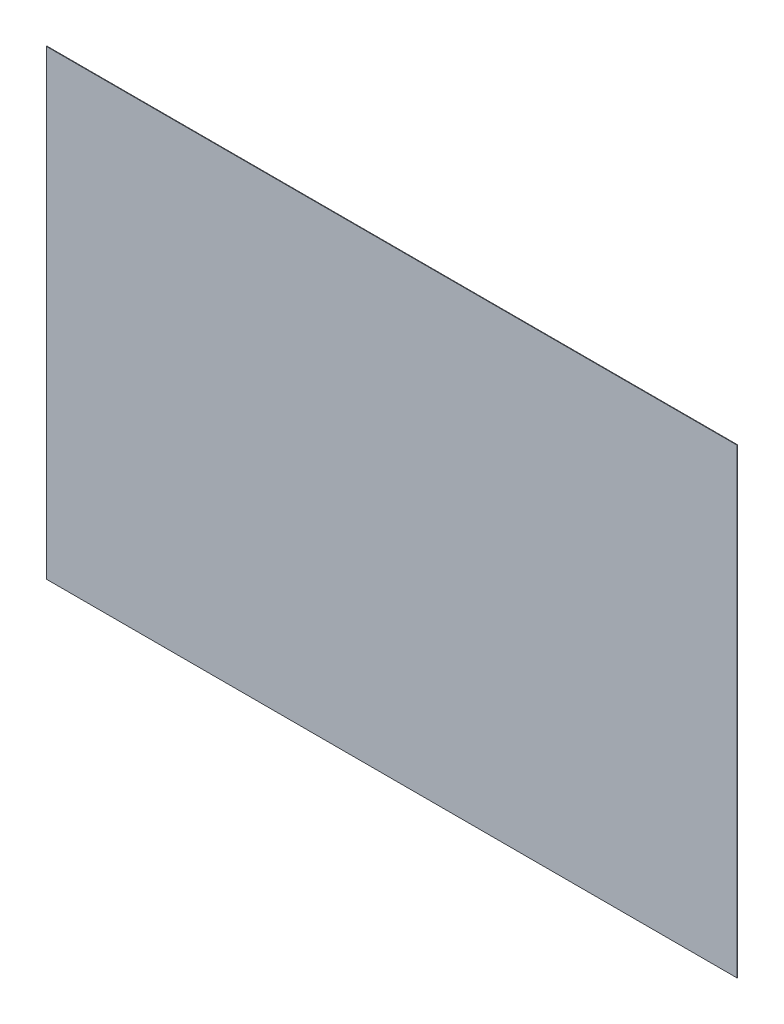
SolidWorks part; units mm, degrees
ref_plane "Front Plane" through (0, 0, 0) normal (0, 0, 1) x (1, 0, 0)
ref_plane "Top Plane" through (0, 0, 0) normal (0, 1, 0) x (1, 0, 0)
ref_plane "Right Plane" through (0, 0, 0) normal (1, 0, 0) x (0, 0, -1)
sketch "Sketch1" plane through (0, 0, 0) normal (0, 0, 1) x (1, 0, 0)
  line L1 (0, 0) -> (2500, 0)
  line L2 (0, 0) -> (0, 1670)
  line L3 (0, 1670) -> (2500, 1670)
  line L4 (2500, 0) -> (2500, 1670)
  dimension "D1" = 2500
  dimension "D2" = 1670
extrude "Boss-Extrude1" add sketch "Sketch1" along normal blind 2
